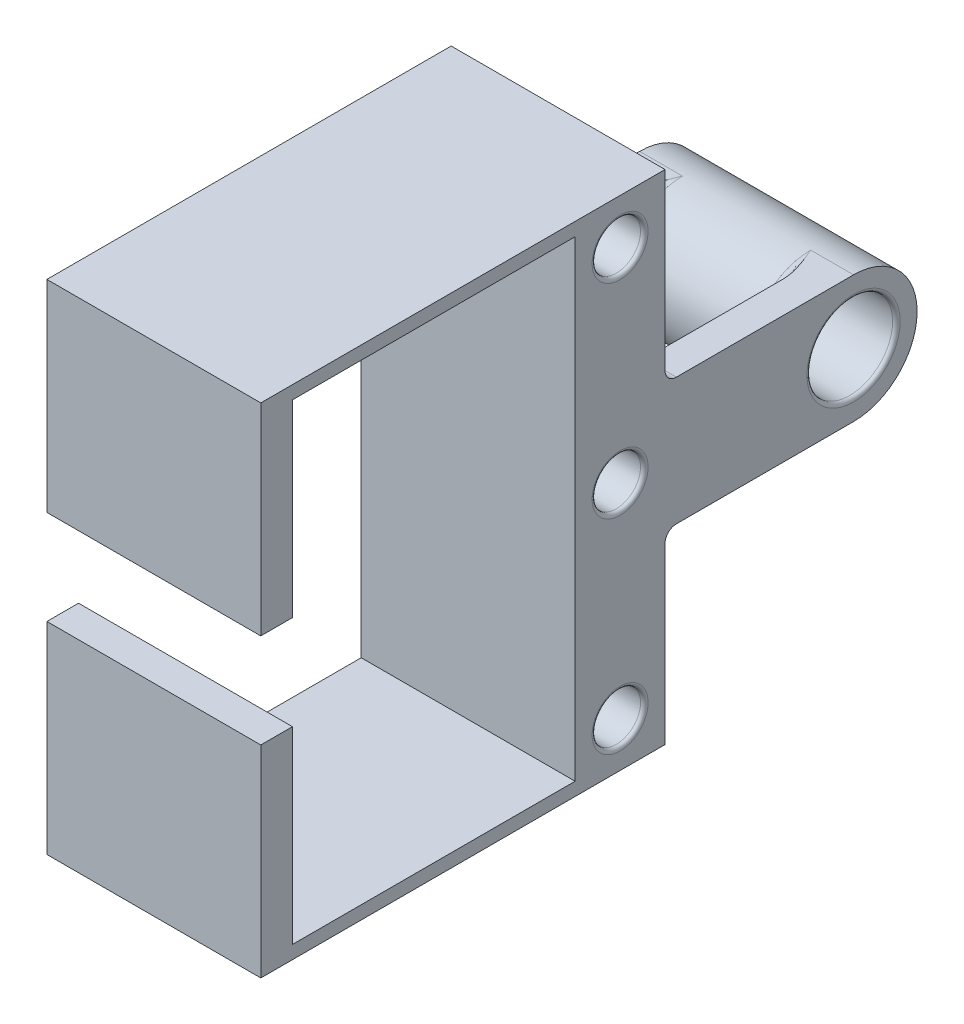
SolidWorks part; units mm, degrees
material "6061-T6 (SS)"
ref_plane "Front Plane" through (0, 0, 0) normal (1, 0, 0) x (0, 1, 0)
ref_plane "Top Plane" through (0, 0, 0) normal (0, 0, 1) x (0, 1, 0)
ref_plane "Right Plane" through (0, 0, 0) normal (0, 1, 0) x (-1, 0, 0)
sketch "Sketch1" plane through (0, 0, 0) normal (1, 0, 0) x (0, 1, 0)
  line L0 (0, 0) -> (0, 79.8704) construction
  line L1 (6.3602, 79.8704) -> (-6.3602, 79.8704) construction
  line L2 (-6.3602, 79.8704) -> (-6.3602, 75.6055)
  line L3 (6.3602, 79.8704) -> (6.3602, 75.6055)
  line L4 (-6.3602, 75.6055) -> (-31.7703, 75.6055)
  line L5 (6.3602, 75.6055) -> (31.7703, 75.6055)
  line L6 (-31.7703, 75.6055) -> (-31.7703, 37.5182)
  line L7 (31.7703, 75.6055) -> (31.7703, 37.5182)
  line L8 (-31.7703, 37.5182) -> (31.7703, 37.5182)
  line L9 (-6.3602, 79.8704) -> (-33.5542, 79.8704)
  line L10 (6.3602, 79.8704) -> (33.5542, 79.8704)
  line L11 (-33.5542, 79.8704) -> (-33.5542, 25.4)
  line L12 (33.5542, 79.8704) -> (33.5542, 25.4)
  line L13 (-33.5542, 25.4) -> (-8.5623, 25.4)
  line L14 (33.5542, 25.4) -> (8.5623, 25.4)
  line L15 (-8.5623, 25.4) -> (-8.5623, 0)
  line L16 (8.5623, 25.4) -> (8.5623, 0)
  line L17 (-8.5623, 25.4) -> (8.5623, 25.4)
  circle A0 centre (0, 0) radius 8.5623
  point P12 (0, 37.5182)
  dimension "D1" = 17.1247
  dimension "D2" = 25.4
  dimension "D3" = 12.1182
  dimension "D4" = 12.7203
  dimension "D5" = 38.0873
  dimension "D6" = 63.5406
  dimension "D7" = 1.7839
  dimension "D8" = 4.2649
extrude "Boss-Extrude1" add sketch "Sketch1" along normal blind 24.5705 contours A0 region at (0, 0, 0)
extrude "Boss-Extrude2" add sketch "Sketch1<5>" against normal blind 4.2505 contours A0 | A0 L16 L17 L15 region at (0, 0, 15.9646) region at (0, 0, 0)
sketch "Sketch1<5>" plane through (0, 0, 0) normal (1, 0, 0) x (0, 1, 0) same geometry as "Sketch1"
extrude "Boss-Extrude3" add sketch "Sketch1<6>" along normal blind 24.5705 and the other way blind 4.2505 contours L13 L17 L14 L12 L10 L3 L5 L7 L8 L6 L4 L2 L9 L11 region at (0, -7.2245, 77.7379)
sketch "Sketch1<6>" plane through (0, 0, 0) normal (1, 0, 0) x (0, 1, 0) same geometry as "Sketch1"
extrude "Boss-Extrude4" add sketch "Sketch1<8>" against normal blind 4.2505 from surface contours A0 L16 L17 L15 region at (0, 0, 15.9646) starting at face at (24.5705, 0, 62.3116)
sketch "Sketch1<8>" plane through (0, 0, 0) normal (1, 0, 0) x (0, 1, 0) same geometry as "Sketch1"
fillet "Fillet1" radius 1.524 8 edges at (20.32, 0, 8.5623) (0, 0, 8.5623) (22.4453, -8.5623, 25.4) (-2.1253, -8.5623, 25.4) (20.32, 0, 25.4) (0, 0, 25.4) (-2.1253, 8.5623, 25.4) (22.4453, 8.5623, 25.4)
sketch "Sketch2" plane through (24.5705, 0, 0) normal (1, 0, 0) x (0, 1, 0)
  line L0 (0, 31.4591) -> (0, 0) construction
  line L1 (-27.4951, 31.4591) -> (27.4951, 31.4591) construction
  line L2 (-10.0863, 25.4) -> (-10.0863, 37.5182) construction
  line L3 (-31.7703, 37.5182) -> (31.7703, 37.5182) construction
  line L5 (-27.4951, 36.1212) -> (-27.4951, 26.797) construction
  line L6 (-27.4951, 31.4591) -> (-32.1572, 31.4591) construction
  line L7 (-33.5542, 79.8704) -> (-33.5542, 25.4) construction
  circle A0 centre (0, 0) radius 5.7683
  arc A1 (-8.5623, 0) -> (8.5623, 0) centre (0, 0) ccw construction
  circle A2 centre (0, 31.4591) radius 3.2651
  circle A3 centre (27.4951, 31.4591) radius 3.2651
  circle A4 centre (-27.4951, 31.4591) radius 3.2651
  circle A5 centre (-27.4951, 26.797) radius 1.397 construction
  circle A6 centre (-27.4951, 36.1212) radius 1.397 construction
  circle A7 centre (-32.1572, 31.4591) radius 1.397 construction
  point P11 (0, 31.4591)
  point P18 (-10.0863, 31.4591)
  dimension "D1" = 2.794
  dimension "D2" = 2.794
extrude "Cut-Extrude1" cut sketch "Sketch2" against normal through all
fillet "Fillet3" radius 0.508 8 edges at (24.5705, 27.4951, 28.194) (-4.2505, 27.4951, 28.194) (24.5705, -27.4951, 28.194) (-4.2505, -27.4951, 28.194) (24.5705, 0, 28.194) (-4.2505, 0, 28.194) (24.5705, 0, -5.7683) (-4.2505, 0, -5.7683)
equation "\"dmax\"= 0.005'maximum allowed deflection"
equation "\"Sa\"= 4 'safety factor"
equation "\"p\"= 3.141592654 'mmmmmmm ... pie"
equation "\"f\"= 750 'load"
equation "\"l\"= 0.8 'strap hanger length"
equation "\"lB\"= 1'Strap Hangdown Length"
equation "\"Ta\"= 0.5008'T Slot Max Width A"
equation "\"Tb\"= 1.0004'T slot clearance a"
equation "\"Tc\"= 1.4995'T slot clearance c"
equation "\"s\"= 39885.37799'Yeild Strength"
equation "\"E\"= 10007604'Modulus of Elasticity"
equation "\"dA\"= ( ( \"Sa\" * \"f\" * ( \"l\" / 2 ) * 32 ) / ( \"p\" * \"s\" ) ) ^ ( 1 / 3 )'Feature A diameter"
equation "\"bB\"= \"dA\"'Feature B Width"
equation "\"hB\"= ( \"f\" * \"Sa\" ) / ( \"s\" * \"dA\" )'Feature B depth"
equation "\"OAL\"= \"l\" + \"hB\"'Overall Length"
equation "\"lC\"= \"Ta\" + ( \"Tb\" * 2 )'Feature C Length"
equation "\"hC\"= ( ( \"f\" * ( \"lC\" ^ 3 ) * \"Sa\" ) / ( \"OAL\" * \"E\" * \"dmax\" * 4 ) ) ^ ( 1 / 3 )'Feature C Depth"
equation "\"lD\"= \"hC\" + \"Tc\"'Feature D length"
equation "\"fD\"= \"f\" / 2'Reaction Force at D"
equation "\"hD\"= ( \"fD\" * \"lD\" * \"Sa\" ) / ( \"OAL\" * \"E\" * \"dmax\" )'Feature D depth"
equation "\"wE\"= \"fD\" / \"hD\"'distributed load for E"
equation "\"hE\"= ( ( \"wE\" * ( \"hD\" ^ 2 ) * ( \"Tc\" ^ 2 ) * \"Sa\" ) / ( \"E\" * \"dmax\" ) ) ^ ( 1 / 3 )'Feature E depth"
equation "\"D3@Sketch1\"=\"hC\"*.75"
equation "\"D1@Sketch1\"=\"dA\""
equation "\"D2@Sketch1\"=\"lB\""
equation "\"D7@Sketch1\"=\"hD\""
equation "\"D8@Sketch1\"=\"hE\""
equation "\"D4@Sketch1\"=\"Ta\""
equation "\"D5@Sketch1\"=\"Tc\""
equation "\"D1@Boss-Extrude1\"=\"l\"+(\"hB\"*1.5)"
equation "\"D1@Boss-Extrude2\"=\"hB\"*1.5"
equation "\"D1@Boss-Extrude3\"=\"l\"+(1.5*\"hB\")"
equation "\"D2@Boss-Extrude3\"=\"hB\"*1.5"
equation "\"D1@Boss-Extrude4\"=\"hB\"*1.5"
